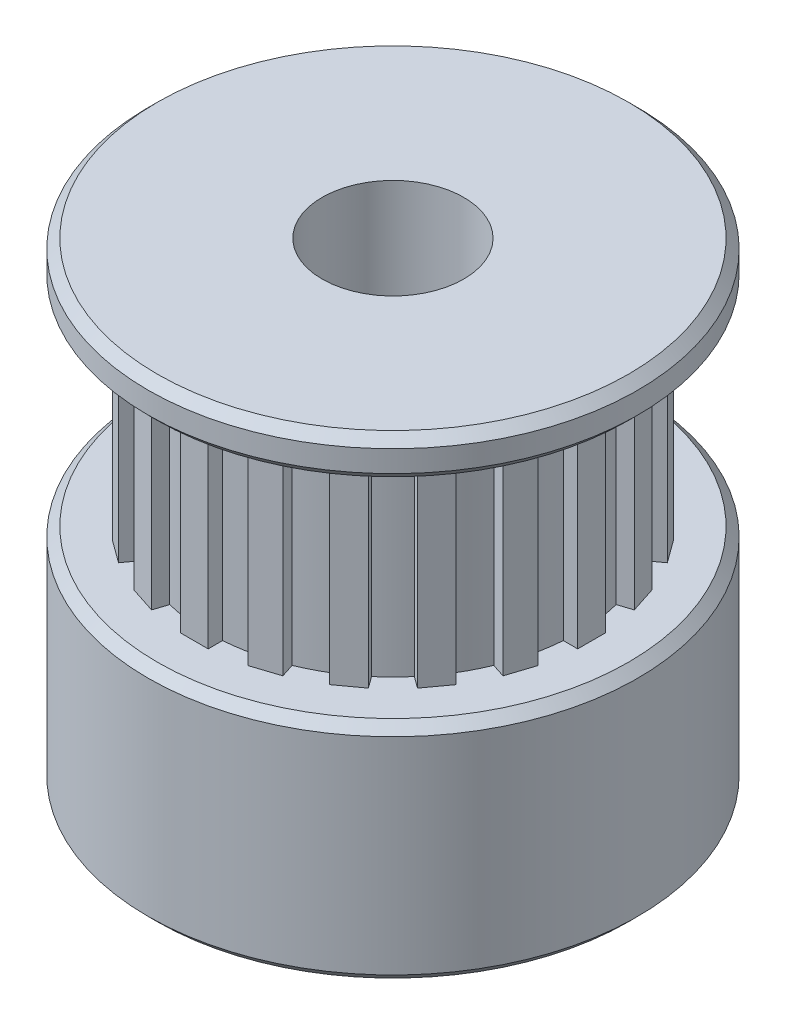
SolidWorks part; units mm, degrees
ref_plane "Front Plane" through (0, 0, 0) normal (0, 0, 1) x (1, 0, 0)
ref_plane "Top Plane" through (0, 0, 0) normal (0, 1, 0) x (1, 0, 0)
ref_plane "Right Plane" through (0, 0, 0) normal (1, 0, 0) x (0, 0, -1)
sketch "Sketch1" plane through (0, 0, 0) normal (0, 1, 0) x (1, 0, 0)
  circle A0 centre (0, 0) radius 7.95
  circle A1 centre (0, 0) radius 2.3
  dimension "D1" = 15.9
  dimension "D2" = 4.6
extrude "Boss-Extrude1" add sketch "Sketch1" along normal blind 7.3
sketch "Sketch2" plane through (0, 7.3, 0) normal (0, 1, 0) x (1, 0, 0)
  line L0 (1.5652, 6.2734) -> (1.4209, 5.8293)
  line L1 (-0.45, 6.45) -> (0.45, 6.45)
  line L2 (-0.45, 6.45) -> (-0.45, 5.9831)
  line L4 (0.45, 6.45) -> (0.45, 5.9831)
  line L7 (1.5652, 6.2734) -> (2.4211, 5.9953)
  line L8 (2.4211, 5.9953) -> (2.2769, 5.5512)
  line L10 (3.4272, 5.4827) -> (3.1527, 5.1049)
  line L11 (3.4272, 5.4827) -> (4.1553, 4.9537)
  line L12 (4.1553, 4.9537) -> (3.8808, 4.5759)
  line L14 (4.9537, 4.1553) -> (4.5759, 3.8808)
  line L15 (4.9537, 4.1553) -> (5.4827, 3.4272)
  line L16 (5.4827, 3.4272) -> (5.1049, 3.1527)
  line L18 (5.9953, 2.4211) -> (5.5512, 2.2769)
  line L19 (5.9953, 2.4211) -> (6.2734, 1.5652)
  line L20 (6.2734, 1.5652) -> (5.8293, 1.4209)
  line L22 (6.45, 0.45) -> (5.9831, 0.45)
  line L23 (6.45, 0.45) -> (6.45, -0.45)
  line L24 (6.45, -0.45) -> (5.9831, -0.45)
  line L26 (6.2734, -1.5652) -> (5.8293, -1.4209)
  line L27 (6.2734, -1.5652) -> (5.9953, -2.4211)
  line L28 (5.9953, -2.4211) -> (5.5512, -2.2769)
  line L30 (5.4827, -3.4272) -> (5.1049, -3.1527)
  line L31 (5.4827, -3.4272) -> (4.9537, -4.1553)
  line L32 (4.9537, -4.1553) -> (4.5759, -3.8808)
  line L34 (4.1553, -4.9537) -> (3.8808, -4.5759)
  line L35 (4.1553, -4.9537) -> (3.4272, -5.4827)
  line L36 (3.4272, -5.4827) -> (3.1527, -5.1049)
  line L38 (2.4211, -5.9953) -> (2.2769, -5.5512)
  line L39 (2.4211, -5.9953) -> (1.5652, -6.2734)
  line L40 (1.5652, -6.2734) -> (1.4209, -5.8293)
  line L42 (0.45, -6.45) -> (0.45, -5.9831)
  line L43 (0.45, -6.45) -> (-0.45, -6.45)
  line L44 (-0.45, -6.45) -> (-0.45, -5.9831)
  line L46 (-1.5652, -6.2734) -> (-1.4209, -5.8293)
  line L47 (-1.5652, -6.2734) -> (-2.4211, -5.9953)
  line L48 (-2.4211, -5.9953) -> (-2.2769, -5.5512)
  line L50 (-3.4272, -5.4827) -> (-3.1527, -5.1049)
  line L51 (-3.4272, -5.4827) -> (-4.1553, -4.9537)
  line L52 (-4.1553, -4.9537) -> (-3.8808, -4.5759)
  line L54 (-4.9537, -4.1553) -> (-4.5759, -3.8808)
  line L55 (-4.9537, -4.1553) -> (-5.4827, -3.4272)
  line L56 (-5.4827, -3.4272) -> (-5.1049, -3.1527)
  line L58 (-5.9953, -2.4211) -> (-5.5512, -2.2769)
  line L59 (-5.9953, -2.4211) -> (-6.2734, -1.5652)
  line L60 (-6.2734, -1.5652) -> (-5.8293, -1.4209)
  line L62 (-6.45, -0.45) -> (-5.9831, -0.45)
  line L63 (-6.45, -0.45) -> (-6.45, 0.45)
  line L64 (-6.45, 0.45) -> (-5.9831, 0.45)
  line L66 (-6.2734, 1.5652) -> (-5.8293, 1.4209)
  line L67 (-6.2734, 1.5652) -> (-5.9953, 2.4211)
  line L68 (-5.9953, 2.4211) -> (-5.5512, 2.2769)
  line L70 (-5.4827, 3.4272) -> (-5.1049, 3.1527)
  line L71 (-5.4827, 3.4272) -> (-4.9537, 4.1553)
  line L72 (-4.9537, 4.1553) -> (-4.5759, 3.8808)
  line L74 (-4.1553, 4.9537) -> (-3.8808, 4.5759)
  line L75 (-4.1553, 4.9537) -> (-3.4272, 5.4827)
  line L76 (-3.4272, 5.4827) -> (-3.1527, 5.1049)
  line L78 (-2.4211, 5.9953) -> (-2.2769, 5.5512)
  line L79 (-2.4211, 5.9953) -> (-1.5652, 6.2734)
  line L80 (-1.5652, 6.2734) -> (-1.4209, 5.8293)
  circle A0 centre (0, 0) radius 2.3 construction
  circle A1 centre (0, 0) radius 2.3
  arc A2 (-5.5512, -2.2769) -> (-5.1049, -3.1527) centre (0, 0) ccw
  arc A3 (-4.5759, -3.8808) -> (-3.8808, -4.5759) centre (0, 0) ccw
  arc A4 (-3.1527, -5.1049) -> (-2.2769, -5.5512) centre (0, 0) ccw
  arc A5 (-1.4209, -5.8293) -> (-0.45, -5.9831) centre (0, 0) ccw
  arc A6 (0.45, -5.9831) -> (1.4209, -5.8293) centre (0, 0) ccw
  arc A7 (2.2769, -5.5512) -> (3.1527, -5.1049) centre (0, 0) ccw
  arc A8 (3.8808, -4.5759) -> (4.5759, -3.8808) centre (0, 0) ccw
  arc A9 (5.1049, -3.1527) -> (5.5512, -2.2769) centre (0, 0) ccw
  arc A10 (5.8293, -1.4209) -> (5.9831, -0.45) centre (0, 0) ccw
  arc A11 (5.9831, 0.45) -> (5.8293, 1.4209) centre (0, 0) ccw
  arc A12 (5.5512, 2.2769) -> (5.1049, 3.1527) centre (0, 0) ccw
  arc A13 (4.5759, 3.8808) -> (3.8808, 4.5759) centre (0, 0) ccw
  arc A14 (3.1527, 5.1049) -> (2.2769, 5.5512) centre (0, 0) ccw
  arc A15 (1.4209, 5.8293) -> (0.45, 5.9831) centre (0, 0) ccw
  arc A16 (0.4532, 5.9829) -> (0.45, 5.9831) centre (0, 0) ccw
  arc A17 (-2.2769, 5.5512) -> (-3.1527, 5.1049) centre (0, 0) ccw
  arc A18 (-3.8808, 4.5759) -> (-4.5759, 3.8808) centre (0, 0) ccw
  arc A19 (-5.1049, 3.1527) -> (-5.5512, 2.2769) centre (0, 0) ccw
  arc A20 (-5.8293, 1.4209) -> (-5.9831, 0.45) centre (0, 0) ccw
  arc A21 (-5.9831, -0.45) -> (-5.8293, -1.4209) centre (0, 0) ccw
  arc A22 (-0.45, 5.9831) -> (-1.4209, 5.8293) centre (0, 0) ccw
  point P4 (0, 6)
  point P88 (0, 0)
  dimension "D1" = 12
  dimension "D2" = 0.9
  dimension "D4" = 20
extrude "Boss-Extrude2" add sketch "Sketch2" along normal blind 6.8 contours L2 A22 L80 L79 L78 A17 L76 L75 L74 A18 L72 L71 L70 A19 L68 L67 L66 A20 L64 L63 L62 A21 L60 L59 L58 A2 L56 L55 L54 A3 L52 L51 L50 A4 L48 L47 L46 A5 L44 L43 L42 A6 L40 L39 L38 A7 L36 L35 L34 A8 L32 region at (1.9368, 7.3, -5.9608)
sketch "Sketch3" plane through (0, 14.1, 0) normal (0, 1, 0) x (1, 0, 0)
  circle A0 centre (0, 0) radius 7.95 construction
  circle A1 centre (0, 0) radius 7.95
  circle A2 centre (0, 0) radius 2.3 construction
  circle A3 centre (0, 0) radius 2.3
extrude "Boss-Extrude3" add sketch "Sketch3" along normal blind 1.3
chamfer "Chamfer1" distance 0.3 angle 45 4 edges at (0, 0, 7.95) (0, 7.3, 7.95) (0, 14.1, 7.95) (0, 15.4, 7.95)
